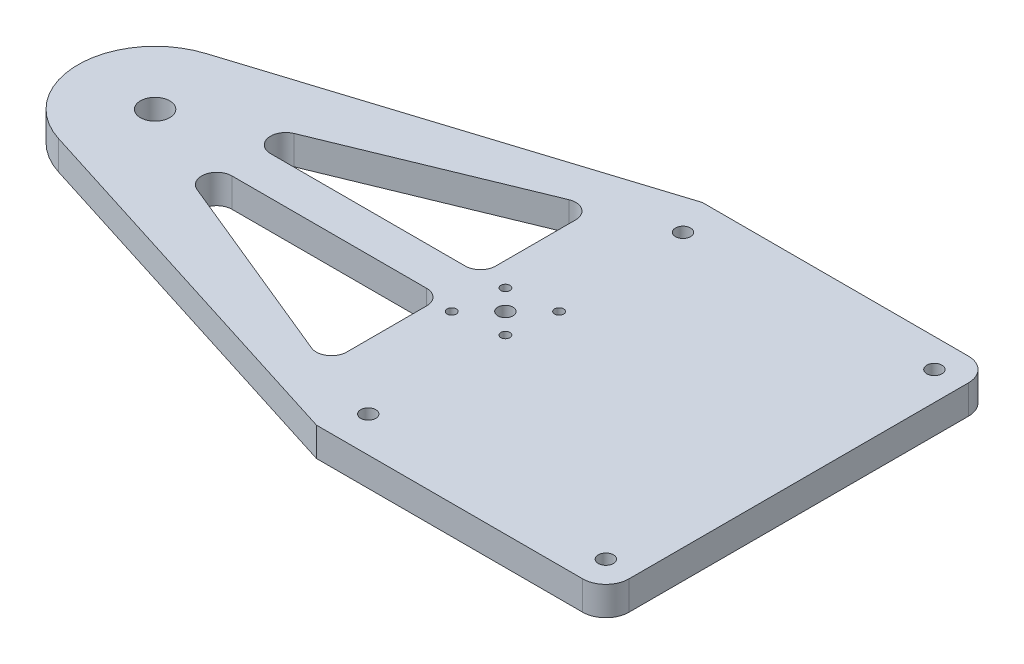
SolidWorks part; units mm, degrees
material "UHMW"
ref_plane "Front Plane" through (0, 0, 0) normal (0, 0, 1) x (1, 0, 0)
ref_plane "Top Plane" through (0, 0, 0) normal (0, 1, 0) x (1, 0, 0)
ref_plane "Right Plane" through (0, 0, 0) normal (1, 0, 0) x (0, 0, -1)
sketch "Sketch1" plane through (0, 0, 0) normal (0, 1, 0) x (1, 0, 0)
  line L0 (-47.625, 0) -> (47.625, 0) construction
  line L1 (-47.625, -63.5) -> (47.625, -63.5)
  line L2 (-47.625, -63.5) -> (-47.625, 63.5)
  line L3 (-47.625, 63.5) -> (47.625, 63.5)
  line L4 (47.625, -63.5) -> (47.625, 63.5)
  line L5 (-47.625, -63.5) -> (47.625, 63.5) construction
  line L6 (-47.625, 63.5) -> (47.625, -63.5) construction
  point P0 (0, 0)
  dimension "D1" = 95.25
  dimension "D2" = 127
  dimension "D3" = 63.5
extrude "Boss-Extrude1" add sketch "Sketch1" along normal blind 9.525
sketch "Sketch4" plane through (0, 9.525, 0) normal (0, 1, 0) x (1, 0, 0)
  line L1 (-47.625, 63.5) -> (-171.916, 24.2193)
  line L5 (-47.625, 63.5) -> (-47.625, -63.5) construction
  line L9 (-47.625, -63.5) -> (-171.916, -24.2193)
  line L10 (-47.625, 63.5) -> (-47.625, -63.5)
  arc A0 (-171.916, 24.2193) -> (-171.916, -24.2193) centre (-164.2618, 0) ccw
  circle A1 centre (-48.9458, 0) radius 2.5 construction
  dimension "D1" = 50.8
  dimension "D2" = 115.316
extrude "Boss-Extrude3" add sketch "Sketch4" against normal blind 9.525
sketch "Sketch5" plane through (0, 9.525, 0) normal (0, 1, 0) x (1, 0, 0)
  line L0 (-48.9458, 0) -> (-31.7264, 0) construction
  line L3 (-48.9458, 0) -> (-91.3931, 0) construction
  circle A0 centre (-164.2618, 0) radius 4.826
  circle A1 centre (-48.9458, 0) radius 2.5
  arc A2 (-171.916, 24.2193) -> (-171.916, -24.2193) centre (-164.2618, 0) ccw construction
  arc A3 (-171.916, 24.2193) -> (-171.916, -24.2193) centre (-164.2618, 0) ccw
  circle A4 centre (-42.2283, -6.7175) radius 1.5
  circle A5 centre (-40.107, 8.8388) radius 1.5
  circle A6 centre (-57.7846, -8.8388) radius 1.5
  circle A7 centre (-55.6633, 6.7175) radius 1.5
  circle A8 centre (-40.107, 8.8388) radius 1.5 construction
  circle A9 centre (-55.6633, 6.7175) radius 1.5 construction
  circle A10 centre (-57.7846, -8.8388) radius 1.5 construction
  circle A11 centre (-42.2283, -6.7175) radius 1.5 construction
  circle A12 centre (-48.9458, 0) radius 2.5 construction
  point P20 (-48.9458, 0)
  dimension "D1" = 9.652
extrude "Cut-Extrude1" cut sketch "Sketch5" against normal through all contours A0 | A1 | A5 | A6 | A7 | A4 region at (-164.2618, 9.525, 0) region at (-48.9458, 9.525, 0)
sketch "Sketch6" plane through (0, 9.525, 0) normal (0, 1, 0) x (1, 0, 0)
  line L0 (-63.5, 6.35) -> (-63.5, -6.35) construction
  line L1 (-63.5, 45.1637) -> (-157.9118, 6.35)
  line L2 (-157.9118, 6.35) -> (-63.5, 6.35)
  line L3 (-63.5, 6.35) -> (-63.5, 45.1637)
  line L4 (-63.5, -6.35) -> (-63.5, -45.1637)
  line L5 (-63.5, -45.1637) -> (-157.9118, -6.35)
  line L6 (-157.9118, -6.35) -> (-63.5, -6.35)
  line L7 (0, 0) -> (-63.5, 0) construction
  line L8 (-189.6618, 75.5498) -> (-189.6618, -75.5498) construction
  line L9 (-47.625, 63.5) -> (-171.916, 24.2193) construction
  arc A0 (-171.916, 24.2193) -> (-171.916, -24.2193) centre (-164.2618, 0) ccw construction
  point P12 (-189.6618, 0)
  dimension "D1" = 31.75
  dimension "D2" = 12.7
  dimension "D3" = 12.7
  dimension "D4" = 63.5
extrude "Cut-Extrude2" cut sketch "Sketch6" against normal through all
fillet "Fillet9" radius 5 6 edges at (-157.9118, 4.7625, 6.35) (-63.5, 4.7625, 6.35) (-63.5, 4.7625, 45.1637) (-63.5, 4.7625, -6.35) (-157.9118, 4.7625, -6.35) (-63.5, 4.7625, -45.1637)
fillet "Fillet10" radius 7.62 2 edges at (47.625, 4.7625, -63.5) (47.625, 4.7625, 63.5)
sketch "Sketch7" plane through (0, 9.525, 0) normal (0, 1, 0) x (1, 0, 0)
  circle A0 centre (-42.2861, -51.8111) radius 2.4892
  circle A1 centre (-42.2861, 51.8111) radius 2.4892
  circle A2 centre (38.2023, 54.0773) radius 2.4892
  circle A3 centre (38.2023, -54.0773) radius 2.4892
extrude "Cut-Extrude3" cut sketch "Sketch7" against normal through all
